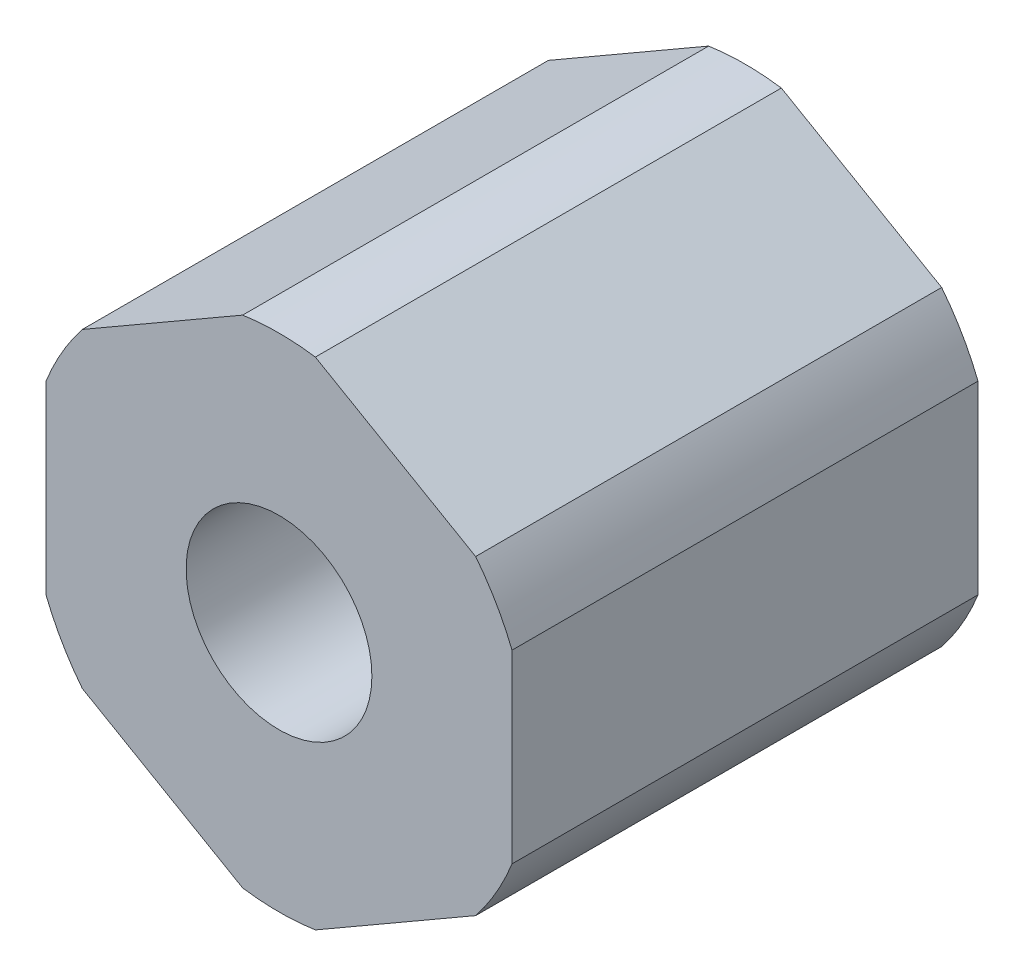
SolidWorks part; units mm, degrees
material "ThunderHex"
ref_plane "Front Plane" through (0, 0, 0) normal (0, 0, 1) x (1, 0, 0)
ref_plane "Top Plane" through (0, 0, 0) normal (0, 1, 0) x (1, 0, 0)
ref_plane "Right Plane" through (0, 0, 0) normal (1, 0, 0) x (0, 0, -1)
ref_plane "End1" through (0, 0, 4.7625) normal (0, 0, 1) x (1, 0, 0)
ref_plane "End2" through (0, 0, -4.7625) normal (0, 0, 1) x (1, 0, 0)
sketch "Sketch1" plane through (0, 0, 0) normal (0, 0, 1) x (1, 0, 0)
  circle A0 centre (0, 0) radius 4.7625
  dimension "D1" = 9.525
extrude "Basic Rod" add sketch "Sketch1" along normal up to surface (4.7625 mm away) and the other way up to surface (4.7625 mm away) up to plane "End1" other way up to plane "End2"
ref_axis "Center Axis" through (0, 0, -38.2778) along (0, 0, 1)
sketch "Sketch8" plane through (0, 0, 0) normal (0, 0, 1) x (1, 0, 0)
  line L0 (-4.0195, 3.1786) -> (-4.7625, 2.7496) construction
  line L1 (-0.743, 5.0703) -> (-4.0195, 3.1786)
  line L2 (-4.7625, 1.8917) -> (-4.7625, -1.8917)
  line L3 (-4.0195, -3.1786) -> (-0.743, -5.0703)
  line L4 (0.743, -5.0703) -> (4.0195, -3.1786)
  line L5 (4.7625, -1.8917) -> (4.7625, 1.8917)
  line L6 (4.0195, 3.1786) -> (0.743, 5.0703)
  line L7 (-4.7625, 2.7496) -> (-4.7625, 1.8917) construction
  line L8 (0, 5.4993) -> (-0.743, 5.0703) construction
  line L9 (0.743, 5.0703) -> (0, 5.4993) construction
  line L10 (4.7625, 2.7496) -> (4.0195, 3.1786) construction
  line L11 (4.7625, 1.8917) -> (4.7625, 2.7496) construction
  line L12 (4.7625, -2.7496) -> (4.7625, -1.8917) construction
  line L13 (4.0195, -3.1786) -> (4.7625, -2.7496) construction
  line L14 (0, -5.4993) -> (0.743, -5.0703) construction
  line L15 (-0.743, -5.0703) -> (0, -5.4993) construction
  line L16 (-4.7625, -2.7496) -> (-4.0195, -3.1786) construction
  line L17 (-4.7625, -1.8917) -> (-4.7625, -2.7496) construction
  circle A0 centre (0, 0) radius 4.7625 construction
  arc A1 (-4.7625, -1.8917) -> (-4.0195, -3.1786) centre (0, 0) ccw
  circle A2 centre (0, 0) radius 4.7625 construction
  arc A3 (-4.7625, 1.8917) -> (-4.7625, -1.8917) centre (0, 0) ccw construction
  arc A4 (-0.743, 5.0703) -> (-4.0195, 3.1786) centre (0, 0) ccw construction
  arc A5 (-4.0195, 3.1786) -> (-4.7625, 1.8917) centre (0, 0) ccw
  arc A6 (4.0195, 3.1786) -> (0.743, 5.0703) centre (0, 0) ccw construction
  arc A7 (0.743, 5.0703) -> (-0.743, 5.0703) centre (0, 0) ccw
  arc A8 (4.7625, -1.8917) -> (4.7625, 1.8917) centre (0, 0) ccw construction
  arc A9 (4.7625, 1.8917) -> (4.0195, 3.1786) centre (0, 0) ccw
  arc A10 (0.743, -5.0703) -> (4.0195, -3.1786) centre (0, 0) ccw construction
  arc A11 (4.0195, -3.1786) -> (4.7625, -1.8917) centre (0, 0) ccw
  arc A12 (-4.0195, -3.1786) -> (-0.743, -5.0703) centre (0, 0) ccw construction
  arc A13 (-0.743, -5.0703) -> (0.743, -5.0703) centre (0, 0) ccw
  dimension "D1" = 10.2489
extrude "THex" add sketch "Sketch8" along normal mid plane 9.525
sketch "Sketch5" plane through (0, 0, 0) normal (0, 0, 1) x (1, 0, 0)
  line L1 (-2.7496, 4.7625) -> (-5.4993, 0)
  line L2 (-5.4993, 0) -> (-2.7496, -4.7625)
  line L3 (-2.7496, -4.7625) -> (2.7496, -4.7625)
  line L4 (2.7496, -4.7625) -> (5.4993, 0)
  line L5 (5.4993, 0) -> (2.7496, 4.7625)
  line L6 (2.7496, 4.7625) -> (-2.7496, 4.7625)
  circle A0 centre (0, 0) radius 4.7625 construction
  circle A2 centre (0, 0) radius 4.7625 construction
extrude "Hex" [suppressed] add sketch "Sketch5" along normal mid plane 9.525
sketch "Sketch7" plane through (0, 0, 0) normal (1, 0, 0) x (0, 0, -1)
  line L0 (0, 0) -> (-50000, 0) construction
  line L1 (-4.7625, 4.4704) -> (-5.7785, 4.4704)
  line L2 (-5.7785, 4.4704) -> (-5.7785, 4.7625)
  line L3 (-5.7785, 4.7625) -> (-6.7945, 4.7625)
  line L4 (-7.3025, 4.2545) -> (-7.3025, 0)
  line L5 (-7.3025, 0) -> (-4.7625, 0)
  line L6 (-4.7625, 0) -> (-4.7625, 4.4704)
  line L7 (-6.7945, 4.7625) -> (-7.3025, 4.2545)
  line L8 (38.2778, 0) -> (-38.2778, 0) construction
  line L9 (-4.7625, 5.2388) -> (-4.7625, -5.2388) construction
  point P7 (-7.3025, 4.7625)
  dimension "D1" = 9.525
  dimension "D4" = 1.016
  dimension "D2" = 0.2921
  dimension "D3" = 2.54
revolve "1stSnapRing" [suppressed] add sketch "Sketch7" angle 360 about axis through (0, 0, -38.2778) along (0, 0, 1)
mirror "2ndSnapRing" [suppressed] about plane through (0, 0, 0) normal (0, 0, 1)
sketch "Sketch2" plane through (0, 0, 0) normal (0, 0, 1) x (1, 0, 0)
  circle A0 centre (0, 0) radius 1.8986
  dimension "D1" = 3.7973
extrude "Internal Cut" cut sketch "Sketch2" against normal through all both and the other way through all
equation "\"Unit Measure\"= \"Length\"'in"
equation "\"D1@Sketch1\"=\"OD\""
equation "\"D1\"= \"Length\""
equation "\"D1@Sketch2\"=\"ID\""
equation "\"Internal Cut\"= IIF ( \"ID\" = 0 ,  suppressed  ,  unsuppressed  ) "
equation "\"D1@Hex\" = \"Length\""
equation "\"Hex\" = IIF ( \"SelectionType\" = 1 , \"suppressed\" , iif ( \"SelectionType\" = 2 , \"suppressed\" , \"unsuppressed\" ) )"
equation "\"OutsideDiameter\"= \"OD\"'in"
equation "\"ThunderHexDia\"= iif ( \"OD\" < .36 , \"OD\" * 1.1 , iif ( \"OD\" < .40 , .4035 , iif ( \"OD\" < .52 , .5415 , \"OD\" * 1.1 ) ) )"
equation "\"D1@Sketch7\"=\"Thickness\""
equation "\"SRDia\"= iif ( \"OD\" = .5 , ( \"OD\" - .468 ) / 2 , iif ( \"OD\" = .375 , ( \"OD\" - .352 ) / 2 , .050 ) )"
equation "\"D2@Sketch7\"= \"SnapRingDepth\""
equation "\"1stSnapRing\"= iif ( \"SnapRingCount\" > 0 , \"unsuppressed\" , \"suppressed\" )"
equation "\"2ndSnapRing\"= iif ( \"SnapRingCount\" = 2 , \"unsuppressed\" , \"suppressed\" )"
equation "\"D1@End1\" = \"Length\" / 2"
equation "\"D1@End2\" = \"Length\""
equation "\"D1@Sketch8\"=\"ThunderHexDia\""
equation "\"D1@THex\" = \"Length\""
equation "\"THex\"= IIF ( \"SelectionType\" = 0 ,  suppressed  , iif ( \"SelectionType\" = 2 ,  suppressed  ,  unsuppressed  )  ) "
